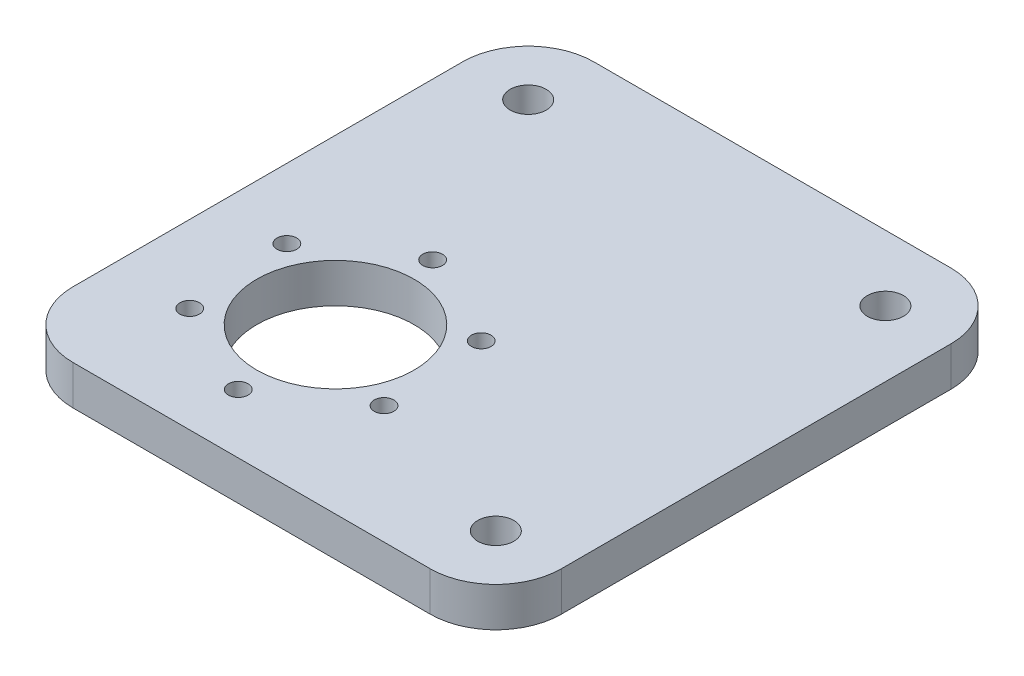
SolidWorks part; units mm, degrees
ref_plane "Front Plane" through (0, 0, 0) normal (0, 0, 1) x (1, 0, 0)
ref_plane "Top Plane" through (0, 0, 0) normal (0, 1, 0) x (1, 0, 0)
ref_plane "Right Plane" through (0, 0, 0) normal (1, 0, 0) x (0, 0, -1)
sketch "Sketch2" plane through (0, 0, 0) normal (0, 1, 0) x (1, 0, 0)
  line L1 (-18.6933, 53.5256) -> (55.7467, 53.5256)
  line L2 (-18.6933, 53.5256) -> (-18.6933, -25.8544)
  line L3 (-18.6933, -25.8544) -> (55.7467, -25.8544)
  line L4 (55.7467, 53.5256) -> (55.7467, -25.8544)
  circle A0 centre (6.3067, -0.8544) radius 12
  dimension "D1" = 24
  dimension "D2" = 74.44
  dimension "D3" = 79.38
extrude "Boss-Extrude1" add sketch "Sketch2" along normal blind 6
sketch "Sketch4" plane through (0, 6, 0) normal (0, 1, 0) x (1, 0, 0)
  circle A0 centre (366.272, -1080.1923) radius 1.25 construction
  circle A1 centre (366.272, -1080.1923) radius 1.25
  circle A2 centre (366.272, -1112.1923) radius 1.25 construction
  circle A3 centre (366.272, -1112.1923) radius 1.25
  circle A4 centre (352.4156, -1104.1923) radius 1.25 construction
  circle A5 centre (352.4156, -1104.1923) radius 1.25
  circle A6 centre (352.4156, -1104.1923) radius 1.25 construction
  circle A7 centre (352.4156, -1104.1923) radius 1.25
  circle A8 centre (352.4156, -1088.1923) radius 1.25 construction
  circle A9 centre (352.4156, -1088.1923) radius 1.25
  circle A10 centre (380.1284, -1088.1923) radius 1.25 construction
  circle A11 centre (380.1284, -1088.1923) radius 1.25
  circle A12 centre (380.1284, -1104.1923) radius 1.25 construction
  circle A13 centre (380.1284, -1104.1923) radius 1.25
sketch "Sketch6" plane through (0, 0, 0) normal (0, -1, 0) x (1, 0, 0)
  line L0 (55.7467, 25.8544) -> (55.7467, -53.5256) construction
  line L1 (55.7467, -53.5256) -> (-18.6933, -53.5256) construction
  line L2 (-18.6933, 25.8544) -> (55.7467, 25.8544) construction
  line L3 (-18.6933, -53.5256) -> (-18.6933, 25.8544) construction
  circle A0 centre (45.7467, 15.8544) radius 2.75
  circle A2 centre (45.7467, -43.5256) radius 2.75
  circle A3 centre (-8.6933, -43.5256) radius 2.75
  dimension "D5" = 5.5
  dimension "D6" = 5.5
  dimension "D7" = 5.5
  dimension "D1" = 10
  dimension "D2" = 10
  dimension "D3" = 10
  dimension "D4" = 10
extrude "Cut-Extrude2" cut sketch "Sketch6" against normal blind 10
sketch "Sketch7" plane through (0, 0, 0) normal (0, -1, 0) x (1, 0, 0)
  circle A0 centre (-8.0868, -6.1332) radius 1.25 construction
  circle A1 centre (-8.0868, -6.1332) radius 1.25
  circle A2 centre (-6.9415, 9.8257) radius 1.25 construction
  circle A3 centre (-6.9415, 9.8257) radius 1.25
  circle A4 centre (20.7003, 7.8419) radius 1.25 construction
  circle A5 centre (20.7003, 7.8419) radius 1.25
  circle A6 centre (19.5549, -8.117) radius 1.25 construction
  circle A7 centre (19.5549, -8.117) radius 1.25
  circle A8 centre (7.4521, 16.8133) radius 1.25 construction
  circle A9 centre (7.4521, 16.8133) radius 1.25
  circle A10 centre (5.1614, -15.1046) radius 1.25 construction
  circle A11 centre (5.1614, -15.1046) radius 1.25
sketch "Sketch8" plane through (0, 0, 0) normal (0, -1, 0) x (1, 0, 0)
  circle A0 centre (7.4521, 16.8133) radius 1.5
  circle A1 centre (20.7003, 7.8419) radius 1.5
  circle A2 centre (19.5549, -8.117) radius 1.5
  circle A3 centre (5.1614, -15.1046) radius 1.5
  circle A4 centre (-8.0868, -6.1332) radius 1.5
  circle A5 centre (-6.9415, 9.8257) radius 1.5
  dimension "D1" = 3
  dimension "D2" = 3
  dimension "D3" = 3
  dimension "D4" = 3
  dimension "D5" = 3
  dimension "D6" = 3
extrude "Cut-Extrude4" cut sketch "Sketch8" against normal through all
fillet "Fillet1" radius 10 4 edges at (55.7467, 3, -53.5256) (-18.6933, 3, -53.5256) (-18.6933, 3, 25.8544) (55.7467, 3, 25.8544)
